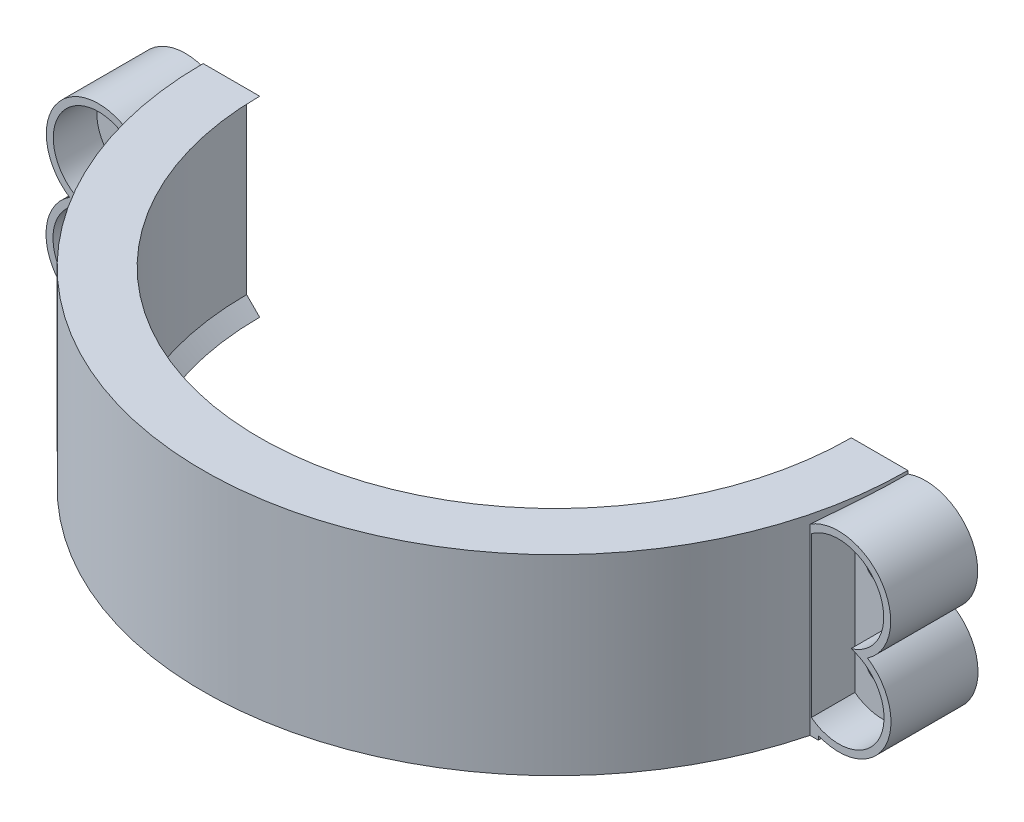
SolidWorks part; units mm, degrees
material "ABS PC"
ref_plane "Front Plane" through (0, 0, 0) normal (0, 0, 1) x (1, 0, 0)
ref_plane "Top Plane" through (0, 0, 0) normal (0, 1, 0) x (1, 0, 0)
ref_plane "Right Plane" through (0, 0, 0) normal (1, 0, 0) x (0, 0, -1)
sketch "Sketch2" plane through (0, 0, 0) normal (1, 0, 0) x (0, 0, -1)
  line L0 (0, 0) -> (-40.5, 0) construction
  line L1 (0, 0) -> (0, 11) construction
  line L24 (-34, -11) -> (-35.5, -9.5)
  line L25 (-35.5, -11) -> (-34, -11)
  line L26 (-40.5, -11) -> (-35.5, -11)
  line L27 (-40.5, 11) -> (-40.5, -11)
  line L28 (-35.5, 9.5) -> (-34, 11)
  line L29 (-35.5, -9.5) -> (-35.5, 9.5)
  line L30 (-34, 11) -> (-35.5, 11)
  line L31 (-35.5, 11) -> (-40.5, 11)
  dimension "D1" = 22
  dimension "D2" = 19
  dimension "D3" = 6.5
  dimension "D4" = 1.5
  dimension "D5" = 1.5
  dimension "D6" = 40.5
revolve "Revolve1" add sketch "Sketch2" angle 180 mid plane about L1
sketch "Sketch3" plane through (0, 0, 0) normal (0, 1, 0) x (1, 0, 0)
  line L0 (0, 0) -> (0, -51.3604) construction
  arc A2 (-40.5, 0) -> (40.5, 0) centre (0, 0) ccw
  arc A3 (-40.5, 0) -> (40.5, 0) centre (0, 0) ccw
  spline S0 degree 3 poles (40.5, 0) (41.5749, -20.6798) (31.8611, -51.1108) (0, -51.3604) knots 0 0 0 0 1 1 1 1
  spline S1 degree 3 poles (-40.5, 0) (-41.5749, -20.6798) (-31.8611, -51.1108) (0, -51.3604) knots 0 0 0 0 1 1 1 1
  dimension "D1" = 0
extrude "Boss-Extrude1" add sketch "Sketch3" against normal up to surface (11 mm away) up to face at (0, -11, 18.625)
sketch "Sketch5" plane through (0, 0, 0) normal (0, 1, 0) x (1, 0, 0)
  line L0 (32.2986, -50) -> (-32.2986, -50)
  line L1 (0, -50) -> (0, 0) construction
  line L2 (32.2986, -50) -> (-4.5209, -70.7981)
  line L3 (-4.5209, -70.7981) -> (-32.2986, -50)
  dimension "D1" = 50
extrude "Cut-Extrude1" cut sketch "Sketch5" against normal up to next
sketch "Sketch6" plane through (0, 0, 50) normal (0, 0, 1) x (1, 0, 0)
  line L0 (-10.6698, -11) -> (10.6698, -11) construction
  line L1 (12.7, -11) -> (-12.7, -11)
  line L2 (12.7, -11) -> (12.7, 7)
  line L3 (12.7, 7) -> (-12.7, 7)
  line L4 (-12.7, -11) -> (-12.7, 7)
  line L5 (12.7, -11) -> (-12.7, 7) construction
  line L6 (12.7, 7) -> (-12.7, -11) construction
  point P0 (0, -2)
  dimension "D1" = 25.4
  dimension "D2" = 18
extrude "Boss-Extrude2" add sketch "Sketch6" against normal up to surface and the other way blind 15 up to face at (10.125, 8.25, 10.125)
sketch "Sketch8" plane through (0, 11, 0) normal (0, 1, 0) x (1, 0, 0)
  line L1 (15.1132, -40.1292) -> (15.1132, -45.0065)
  line L2 (12.7, -65) -> (12.7, -38.4572) construction
  line L3 (0, -65) -> (0, 0) construction
  line L4 (12.7, -65) -> (-12.7, -65) construction
  line L5 (-15.1132, -40.1292) -> (-15.1132, -45.0065)
  line L6 (2, -62) -> (-2, -62)
  line L7 (2, -62) -> (2, -42.1155)
  line L8 (2, -42.1155) -> (-2, -42.1155)
  line L9 (-2, -62) -> (-2, -42.1155)
  line L10 (2, -62) -> (-2, -42.1155) construction
  line L11 (2, -42.1155) -> (-2, -62) construction
  arc A0 (15.1132, -40.1292) -> (33.442, -26.8401) centre (0, 0) ccw
  arc A1 (-15.1132, -40.1292) -> (-33.442, -26.8401) centre (0, 0) cw
  spline S0 degree 3 poles (15.1132, -45.0065) (20.5532, -43.0961) (30.7451, -32.7165) (33.442, -26.8401) knots 0 0 0 0 1 1 1 1
  spline S1 degree 3 poles (-15.1132, -45.0065) (-20.5532, -43.0961) (-30.7451, -32.7165) (-33.442, -26.8401) knots 0 0 0 0 1 1 1 1
  point P1 (0, -52.0577)
  dimension "D1" = 4
  dimension "D2" = 3
extrude "Cut-Extrude3" cut sketch "Sketch8" against normal through all
fillet "Fillet1" radius 5 4 edges at (-12.7, 7, 51.7286) (12.7, 7, 51.7286) (-12.7, -2, 65) (12.7, -2, 65) first distance on face at (-12.7, -1.3333, 50.954) first distance on face at (12.7, -1.3333, 50.954)
sketch "Sketch9" plane through (0, 0, 0) normal (0, 0, 1) x (1, 0, 0)
  line L0 (40.579, -11) -> (40.5, 11) construction
  line L1 (12.7, -11) -> (40.579, -11) construction
  line L2 (40.5, 11) -> (-40.5, 11) construction
  line L3 (0, 10.25) -> (0, -10.25) construction
  arc A0 (39.2229, -0.0119) -> (45.8561, 0.0119) centre (42.5574, -5) ccw
  circle A1 centre (42.5574, -5) radius 2
  arc A2 (45.8561, 0.0119) -> (39.2229, -0.0119) centre (42.5216, 5) ccw
  circle A3 centre (42.5216, 5) radius 2
  circle A4 centre (-42.5574, -5) radius 2
  arc A5 (-39.2229, -0.0119) -> (-45.8561, 0.0119) centre (-42.5574, -5) cw
  circle A6 centre (-42.5216, 5) radius 2
  arc A7 (-45.8561, 0.0119) -> (-39.2229, -0.0119) centre (-42.5216, 5) cw
  dimension "D1" = 4
  dimension "D2" = 4
  dimension "D3" = 4
  dimension "D4" = 4
extrude "Boss-Extrude3" add sketch "Sketch9" along normal blind 10
sketch "Sketch10" plane through (0, 0, 10) normal (0, 0, 1) x (1, 0, 0)
  line L0 (39.4078, -9.1376) -> (39.4078, 9.1647)
  line L9 (0, 0) -> (0, 11.9089) construction
  line L12 (-40.9987, 0.8) -> (-40.046, 0.8)
  line L13 (-40.046, 0.8) -> (-40.046, 9.5729)
  line L14 (-40.9987, -9.9609) -> (-40.9987, 0.8)
  line L16 (-39.4078, -9.1376) -> (-39.4078, 9.1647)
  arc A0 (43.9677, 0.0051) -> (39.4078, -9.1376) centre (42.5574, -5) cw
  arc A1 (39.4078, 9.1647) -> (43.9677, 0.0051) centre (42.5216, 5) cw
  arc A8 (-40.046, 9.5729) -> (-43.9677, 0.0051) centre (-42.5216, 5) ccw
  arc A9 (-43.9677, 0.0051) -> (-40.9987, -9.9609) centre (-42.5574, -5) ccw
  arc A10 (-39.4078, 9.1647) -> (-43.9677, 0.0051) centre (-42.5216, 5) ccw
  arc A11 (-43.9677, 0.0051) -> (-39.4078, -9.1376) centre (-42.5574, -5) ccw
  dimension "D1" = 0.8
extrude "Cut-Extrude4" cut sketch "Sketch10" against normal blind 5 and the other way through all
sketch "Sketch11" plane through (0, 11, 0) normal (0, 1, 0) x (1, 0, 0)
  line L2 (48.5216, -10) -> (39.246, -10)
  line L3 (-48.5216, -10) -> (-39.246, -10)
  line L4 (40.5, 0) -> (34, 0)
  line L5 (-34, 0) -> (-40.5, 0)
  line L8 (48.5216, -10) -> (48.5216, -69.7489)
  line L9 (48.5216, -69.7489) -> (-48.5216, -69.7489)
  line L10 (-48.5216, -69.7489) -> (-48.5216, -10)
  arc A4 (-40.5, 0) -> (40.5, 0) centre (0, 0) ccw
  arc A5 (-34, 0) -> (34, 0) centre (0, 0) ccw
  arc A6 (-39.246, -10) -> (39.246, -10) centre (0, 0) ccw
  dimension "D1" = 0
extrude "Cut-Extrude5" cut sketch "Sketch11" against normal through all
